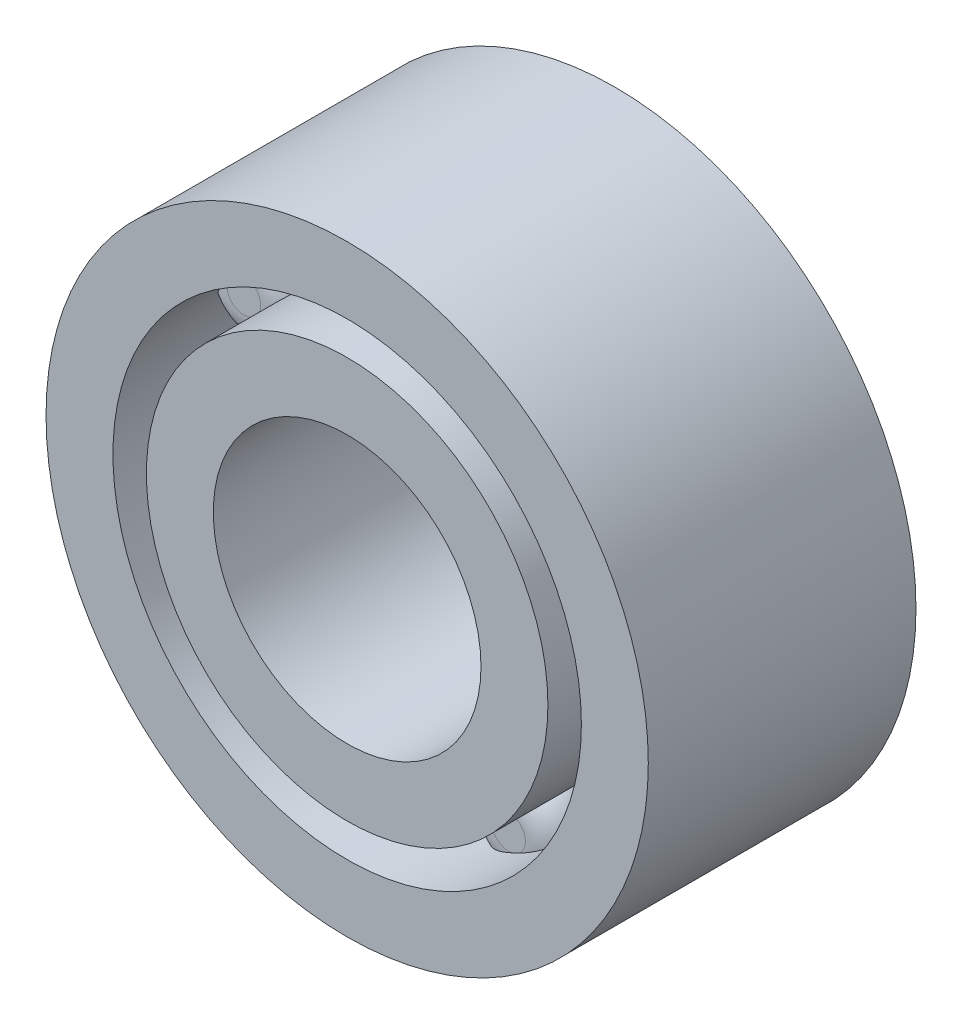
SolidWorks part; units mm, degrees
material "AISI 1020 Steel, Cold Rolled"
ref_plane "Front Plane" through (0, 0, 0) normal (0, 0, 1) x (1, 0, 0)
ref_plane "Top Plane" through (0, 0, 0) normal (0, 1, 0) x (1, 0, 0)
ref_plane "Right Plane" through (0, 0, 0) normal (1, 0, 0) x (0, 0, -1)
sketch "Sketch1" plane through (0, 0, 0) normal (0, 0, 1) x (1, 0, 0)
  circle A0 centre (0, 0) radius 2
  circle A1 centre (0, 0) radius 3
  circle A2 centre (0, 0) radius 3.5
  circle A3 centre (0, 0) radius 4.5
  dimension "D1" = 9
  dimension "D2" = 4
  dimension "D3" = 1
  dimension "D4" = 1
extrude "Boss-Extrude1" add sketch "Sketch1" along normal blind 4 contours A1 A0 | A3 A2 region at (-2.9151, 0, 0) region at (-4.3727, 0, 0)
sketch "Sketch2" plane through (0, 0, 4) normal (0, 0, 1) x (1, 0, 0)
  circle A0 centre (0, 3.2549) radius 0.7521
  circle A1 centre (2.5448, 2.0294) radius 0.7521
  circle A2 centre (3.1733, -0.7243) radius 0.7521
  circle A3 centre (1.4123, -2.9326) radius 0.7521
  circle A4 centre (-1.4123, -2.9326) radius 0.7521
  circle A5 centre (-3.1733, -0.7243) radius 0.7521
  circle A6 centre (-2.5448, 2.0294) radius 0.7521
  point P16 (0, 0)
  dimension "D1" = 7
extrude "Boss-Extrude2" add sketch "Sketch2" along normal blind 1 and the other way blind 1 from offset 2 offset against normal yes
fillet "Fillet1" radius 0.5 14 edges at (3.2545, 0.0234, 1) (0.7014, -3.1781, 1) (-2.0474, -2.5299, 1) (-2.9221, -1.4332, 1) (0.747, 3.1677, 1) (2.0109, 2.5591, 1) (-2.9424, 1.391, 1) (-2.9424, 1.391, 3) (-2.9221, -1.4332, 3) (-0.7014, -3.1781, 3) (2.0474, -2.5299, 3) (3.2545, 0.0234, 3) (2.9424, 1.391, 3) (0.747, 3.1677, 3)
